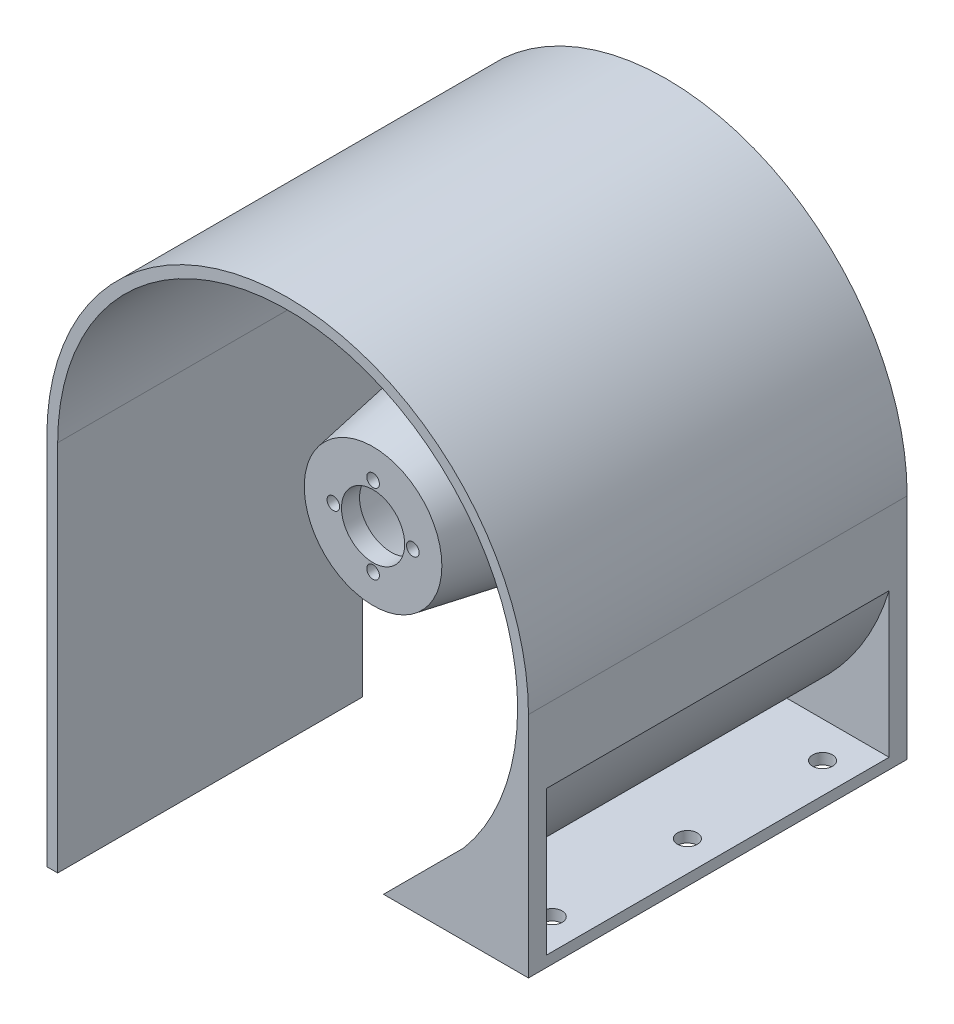
SolidWorks part; units mm, degrees
ref_plane "Front Plane" through (0, 0, 0) normal (0, 0, 1) x (1, 0, 0)
ref_plane "Top Plane" through (0, 0, 0) normal (0, 1, 0) x (1, 0, 0)
ref_plane "Right Plane" through (0, 0, 0) normal (1, 0, 0) x (0, 0, -1)
sketch "Sketch1" plane through (0, 0, 0) normal (0, 0, 1) x (1, 0, 0)
  line L0 (0, 0) -> (31.75, 0) construction
  line L1 (-34.925, 0) -> (-34.925, -63.5)
  line L4 (98.425, -64.8339) -> (98.425, 0)
  line L7 (-34.925, -63.5) -> (-34.925, -103.175)
  line L8 (-34.925, -103.175) -> (98.425, -103.175)
  line L9 (98.425, -64.8339) -> (98.425, -103.175)
  line L10 (-34.925, -63.5) -> (98.425, -103.175) construction
  line L11 (-34.925, -103.175) -> (98.425, -64.8339) construction
  circle A0 centre (0, 0) radius 25.4 construction
  circle A2 centre (31.75, 0) radius 63.5 construction
  arc A3 (98.425, 0) -> (-34.925, 0) centre (31.75, 0) ccw
  circle A4 centre (31.75, 0) radius 66.675 construction
  point P16 (32.89, -83.6767)
  dimension "D1" = 50.8
  dimension "D3" = 127
  dimension "D4" = 31.75
  dimension "D5" = 3.175
extrude "Boss-Extrude1" add sketch "Sketch1" along normal blind 104.85
sketch "Sketch2" plane through (0, 0, 104.85) normal (0, 0, 1) x (1, 0, 0)
  line L0 (31.75, -66.675) -> (31.75, -103.175)
  line L1 (-34.925, -103.175) -> (98.425, -103.175) construction
  line L2 (31.75, -103.175) -> (98.425, -103.175)
  line L3 (98.425, -103.175) -> (98.425, 0)
  arc A0 (31.75, -66.675) -> (98.425, 0) centre (31.75, 0) ccw
extrude "Cut-Extrude1" cut sketch "Sketch2" against normal up to next
sketch "Sketch3" plane through (0, 0, 0) normal (0, 0, -1) x (-1, 0, 0)
  line L0 (-31.75, -93.175) -> (34.925, -93.175) construction
  line L1 (-31.75, -103.175) -> (-31.75, -66.675) construction
  line L2 (34.925, 0) -> (34.925, -103.175) construction
  line L3 (-31.75, -73.175) -> (34.925, -73.175) construction
  line L4 (34.925, -103.175) -> (-31.75, -103.175) construction
  line L5 (1.5875, -93.175) -> (1.5875, -73.175) construction
  line L6 (1.5875, -83.175) -> (-26.4696, -83.175) construction
  circle A0 centre (-21.75, -93.175) radius 2.665
  circle A1 centre (-21.75, -73.175) radius 2.665
  circle A2 centre (24.925, -93.175) radius 2.665
  circle A3 centre (24.925, -73.175) radius 2.665
  dimension "D3" = 5.33
  dimension "D4" = 10
  dimension "D1" = 20
  dimension "D2" = 10
extrude "Cut-Extrude2" cut sketch "Sketch3" against normal up to next
sketch "Sketch5" plane through (0, 0, 0) normal (0, 0, -1) x (-1, 0, 0)
  line L0 (-31.75, -66.675) -> (-98.425, -66.675)
  line L1 (-98.425, -66.675) -> (-98.425, 0)
  arc A0 (34.925, 0) -> (-31.75, -66.675) centre (-31.75, 0) ccw construction
  arc A1 (-98.425, 0) -> (-31.75, -66.675) centre (-31.75, 0) ccw
extrude "Boss-Extrude2" add sketch "Sketch5" against normal up to surface (104.85 mm away) up to face at (24.415, -73.175, 104.85)
sketch "Sketch6" plane through (0, 0, 0) normal (0, 0, -1) x (-1, 0, 0)
  line L1 (-31.75, -66.675) -> (34.925, -66.675)
  line L2 (-31.75, -66.675) -> (-31.75, -103.175)
  line L3 (-31.75, -103.175) -> (34.925, -103.175)
  line L4 (34.925, -66.675) -> (34.925, -103.175)
  line L5 (-31.75, -66.675) -> (34.925, -103.175) construction
  line L6 (-31.75, -103.175) -> (34.925, -66.675) construction
  point P4 (1.5875, -84.925)
extrude "Cut-Extrude3" cut sketch "Sketch6" against normal up to next
sketch "Sketch7" plane through (0, -66.675, 0) normal (0, -1, 0) x (1, 0, 0)
  line L4 (98.425, 0) -> (98.425, 104.85)
  line L5 (98.425, 104.85) -> (-34.925, 104.85)
  line L6 (-34.925, 104.85) -> (-34.925, 0)
  line L7 (-34.925, 0) -> (98.425, 0)
  line L8 (98.425, 0) -> (98.425, 104.85)
  line L9 (98.425, 104.85) -> (-34.925, 104.85)
  line L10 (-34.925, 104.85) -> (-34.925, 0)
  line L11 (-34.925, 0) -> (98.425, 0)
  dimension "D1" = 0
extrude "Cut-Extrude4" cut sketch "Sketch7" against normal blind 3.5
ref_plane "Plane1" through (0, 0, 5) normal (0, 0, -1) x (-1, 0, 0)
sketch "Sketch8" plane through (0, 0, 5) normal (0, 0, -1) x (-1, 0, 0)
  line L1 (-98.425, -60.175) -> (-98.425, 0)
  line L2 (-98.425, -60.175) -> (34.925, -60.175)
  line L3 (-98.425, -60.175) -> (-66.8723, -60.175)
  arc A1 (-98.425, -20.225) -> (-66.8723, -60.175) centre (-31.75, 0) ccw
  dimension "D2" = 3
extrude "Cut-Extrude5" cut sketch "Sketch8" against normal offset from surface (94.85 mm away) 5 contours A1 L1 L3 region at (89.2304, -48.7887, 5) up to face at (31.75, -14.9188, 104.85)
sketch "Sketch9" plane through (0, -60.175, 0) normal (0, 1, 0) x (1, 0, 0)
  line L0 (100, 0) -> (100, -950) construction
  line L1 (100, 0) -> (100, -950) construction
  line L2 (90, -99.85) -> (90, -5) construction
  line L3 (98.425, -99.85) -> (66.8723, -99.85) construction
  line L4 (98.425, -5) -> (66.8723, -5) construction
  circle A0 centre (90, -89.85) radius 2.75
  circle A1 centre (90, -15) radius 2.75
  circle A2 centre (90, -52.425) radius 2.75
  dimension "D2" = 10
  dimension "D4" = 5.5
  dimension "D1" = 10
  dimension "D3" = 10
extrude "Cut-Extrude6" cut sketch "Sketch9" against normal blind 5
sketch "Sketch10" plane through (0, 0, 104.85) normal (0, 0, 1) x (1, 0, 0)
  line L0 (80.5279, -40.9295) -> (58.2824, -63.175)
  line L1 (98.425, -63.175) -> (-34.925, -63.175) construction
  line L2 (58.2824, -63.175) -> (31.75, -63.175)
  line L3 (-31.925, 0) -> (-31.925, -63.175)
  line L4 (-31.925, -63.175) -> (31.75, -63.175)
  arc A2 (95.425, 0) -> (-31.925, 0) centre (31.75, 0) ccw
  arc A3 (95.425, 0) -> (-31.925, 0) centre (31.75, 0) ccw
  arc A4 (80.5279, -40.9295) -> (-31.925, 0) centre (31.75, 0) ccw
  line M4 (-34.925, -63.175) -> (98.425, -63.175)
  dimension "D2" = 45
  dimension "D1" = 3
extrude "Cut-Extrude7" cut sketch "Sketch10" against normal offset from surface (99.85 mm away) 5 contours L0 A4 A3 L3 M4 region at (28.7964, -3.2991, 104.85) up to face at (31.75, -14.9188, 0)
sketch "Sketch11" plane through (0, -63.175, 0) normal (0, -1, 0) x (1, 0, 0)
  line L0 (-31.925, 5) -> (-31.925, 104.85) construction
  line L1 (-34.925, 104.85) -> (-31.925, 104.85)
  line L2 (-34.925, 104.85) -> (-34.925, 20.5)
  line L3 (-34.925, 20.5) -> (-31.925, 20.5)
  line L4 (-31.925, 104.85) -> (-31.925, 20.5)
  line L5 (-34.925, 104.85) -> (-31.925, 20.5) construction
  line L6 (-34.925, 20.5) -> (-31.925, 104.85) construction
  line L7 (-34.925, 0) -> (98.425, 0) construction
  point P4 (-33.425, 62.675)
  dimension "D1" = 20.5
extrude "Boss-Extrude3" add sketch "Sketch11" along normal blind 40
sketch "Sketch12" plane through (0, 0, 5) normal (0, 0, 1) x (1, 0, 0)
  circle A0 centre (31.75, 0) radius 19.05
  dimension "D1" = 38.1
extrude "Boss-Extrude4" add sketch "Sketch12" along normal blind 76.2
chamfer "Chamfer1" distance 76.2 angle 10 1 edges at (50.8, 0, 5) first distance on face at (50.8, 0, 81.2)
shell "Shell1" thickness 5 removed face at (31.75, -14.9188, 0)
sketch "Sketch13" plane through (0, 0, 81.2) normal (0, 0, 1) x (1, 0, 0)
  circle A0 centre (31.75, 0) radius 8.75
  dimension "D1" = 17.5
extrude "Cut-Extrude8" cut sketch "Sketch13" against normal up to next
sketch "Sketch14" plane through (0, 0, 81.2) normal (0, 0, 1) x (1, 0, 0)
  circle A0 centre (31.75, 0) radius 11 construction
  circle A1 centre (31.75, 11) radius 1.75
  circle A2 centre (42.75, 0) radius 1.75
  circle A3 centre (31.75, 0) radius 11 construction
  circle A4 centre (31.75, -11) radius 1.75
  circle A5 centre (31.75, 0) radius 11 construction
  circle A6 centre (20.75, 0) radius 1.75
  circle A7 centre (31.75, 0) radius 11 construction
  point P17 (31.75, 0)
  dimension "D1" = 22
  dimension "D2" = 3.5
  dimension "D3" = 4
extrude "Cut-Extrude9" cut sketch "Sketch14" against normal up to next
